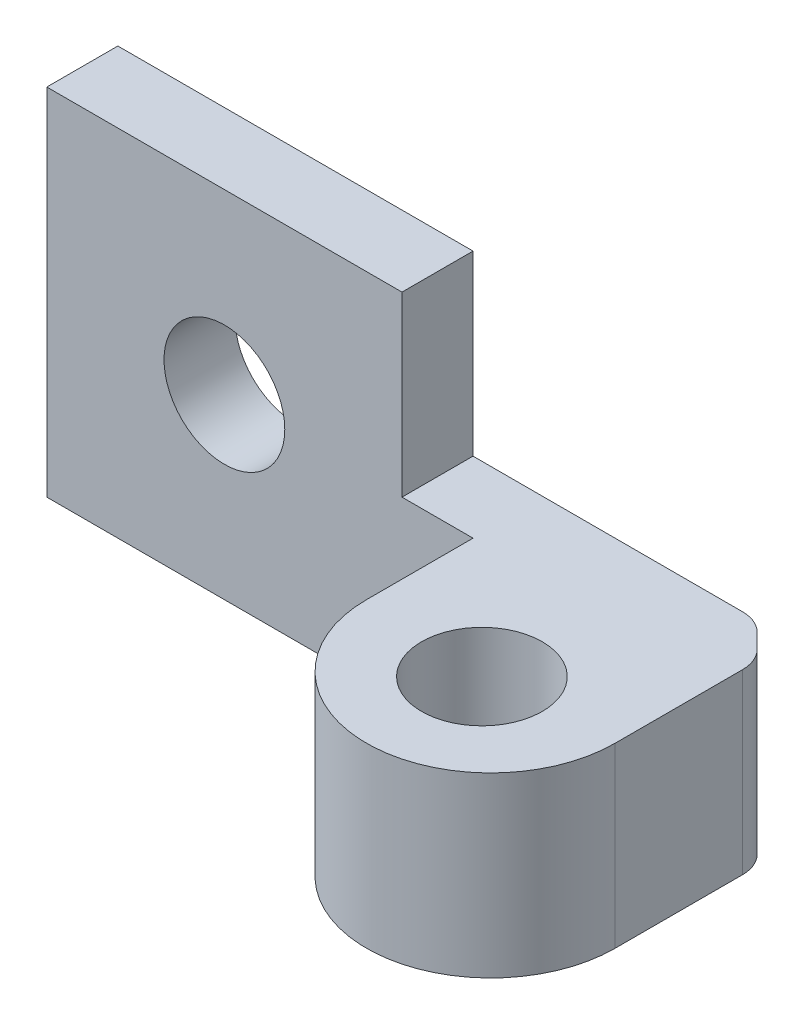
SolidWorks part; units mm, degrees
material "Acciaio in lega fuso"
ref_plane "Piano frontale" through (0, 0, 0) normal (0, 0, 1) x (1, 0, 0)
ref_plane "Piano superiore" through (0, 0, 0) normal (0, 1, 0) x (1, 0, 0)
ref_plane "Piano destro" through (0, 0, 0) normal (1, 0, 0) x (0, 0, -1)
sketch "Schizzo1" plane through (0, 0, 0) normal (0, 0, 1) x (1, 0, 0)
  line L0 (5, 5) -> (5, 0)
  line L1 (5, -5) -> (-5, -5)
  line L2 (5, 0) -> (14, 0)
  line L3 (5, 5) -> (-5, 5)
  line L4 (-5, -5) -> (-5, 5)
  line L5 (5, -5) -> (-5, 5) construction
  line L6 (5, 5) -> (-5, -5) construction
  line L7 (14, 0) -> (14, -5)
  line L8 (14, -5) -> (5, -5)
  line L9 (0, 0) -> (5, 0) construction
  point P0 (0, 0)
  dimension "D1" = 10
  dimension "D2" = 19
extrude "Estrusione-Estrusione1" add sketch "Schizzo1" along normal blind 2
sketch "Schizzo2" plane through (0, 0, 2) normal (0, 0, 1) x (1, 0, 0)
  line L0 (-5, -5) -> (14, -5) construction
  line L1 (14, 0) -> (7, 0)
  line L2 (14, 0) -> (14, -5)
  line L3 (14, -5) -> (7, -5)
  line L4 (7, 0) -> (7, -5)
  dimension "D1" = 7
extrude "Estrusione-Estrusione2" add sketch "Schizzo2" along normal blind 6.5
hole_wizard "Foro per Vite M3-1" positions "Schizzo4" profile "Schizzo3" hole size "M3" standard "Ansi Metric"
sketch "Schizzo4" plane through (0, 0, 2) normal (0, 0, 1) x (1, 0, 0)
  point P0 (0, 0)
sketch "Schizzo3" plane through (0, 0, 2) normal (1, 0, 0) x (0, -1, 0)
  line L0 (0, 0) -> (0, 3.0215)
  line L1 (0, 3.0215) -> (1.7, 2)
  line L2 (1.7, 2) -> (1.7, 0)
  line L5 (1.7, 0) -> (0, 0)
  line L10 (0, 3.0215) -> (-1.7, 2) construction
  line L11 (0, -6.35) -> (0, 107.95) construction
  dimension "Hole Dia." = 3.4
  dimension "Hole Depth" = 2
  dimension "Drill Angle" = 118
hole_wizard "Foro per Vite M3-2" positions "Schizzo6" profile "Schizzo5" hole size "M3" standard "Ansi Metric" end condition through all
sketch "Schizzo6" plane through (0, -5, 0) normal (0, -1, 0) x (-1, 0, 0)
  line L0 (-10.5, -8.5) -> (-10.5, -5.25) construction
  line L1 (-7, -8.5) -> (-14, -8.5) construction
  line L2 (-10.5, -5.25) -> (-7, -5.25) construction
  line L3 (-7, -8.5) -> (-7, -2) construction
  point P0 (-10.5, -5.25)
sketch "Schizzo5" plane through (10.5, -5, 5.25) normal (1, 0, 0) x (0, 0, -1)
  line L0 (0, 0) -> (0, 10)
  line L1 (0, 10) -> (1.7, 10)
  line L2 (1.7, 10) -> (1.7, 0)
  line L5 (1.7, 0) -> (0, 0)
  line L11 (0, -6.35) -> (0, 107.95) construction
  dimension "Thru Hole Dia." = 3.4
  dimension "Thru Hole Depth" = 10
fillet "Raccordo1" 2 edges at (7, -2.5, 8.5) (14, -2.5, 8.5) type full round first side face at (7, -1.875, 6.875) second side face at (14, -2.5, 4.25) middle face at (10.5, -2.5, 8.5)
chamfer "Smusso1" distance 1 angle 45 1 edges at (14, -2.5, 0)
fillet "Raccordo2" radius 1 2 edges at (13, -2.5, 0) (14, -2.5, 1)
